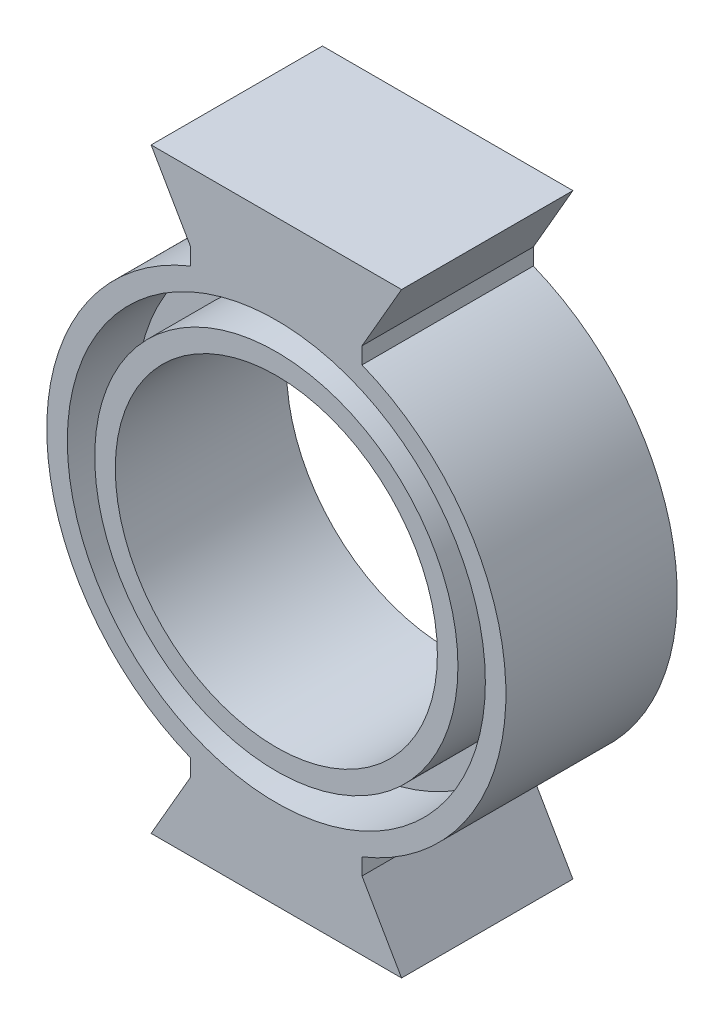
SolidWorks part; units mm, degrees
ref_plane "Front" through (0, 0, 0) normal (0, 0, 1) x (1, 0, 0)
ref_plane "Top" through (0, 0, 0) normal (0, 1, 0) x (1, 0, 0)
ref_plane "Right" through (0, 0, 0) normal (1, 0, 0) x (0, 0, -1)
sketch "Sketch1" plane through (0, 0, 0) normal (0, 0, 1) x (1, 0, 0)
  circle A0 centre (0, 0) radius 5.969
  circle A1 centre (0, 0) radius 8.509
  dimension "D1" = 11.938
  dimension "D2" = 17.018
extrude "Boss-Extrude1" add sketch "Sketch1" along normal blind 6.35
sketch "Sketch2" plane through (0, 0, 6.35) normal (0, 0, 1) x (1, 0, 0)
  circle A0 centre (0, 0) radius 6.731
  circle A1 centre (0, 0) radius 7.747
  dimension "D1" = 13.462
  dimension "D2" = 15.494
extrude "Cut-Extrude1" cut sketch "Sketch2" against normal blind 2.54
sketch "Sketch3" plane through (0, 0, 0) normal (0, 0, 1) x (1, 0, 0)
  line L4 (-3.175, 7.8945) -> (-3.175, 8.509)
  line L5 (3.175, 7.8945) -> (3.175, 8.509)
  line L6 (3.175, 8.509) -> (4.6415, 11.049)
  line L7 (4.6415, 11.049) -> (-4.6415, 11.049)
  line L8 (-4.6415, 11.049) -> (-3.175, 8.509)
  line L9 (-3.175, 8.509) -> (3.175, 8.509) construction
  circle A2 centre (0, 0) radius 8.509 construction
  arc A3 (-3.175, 7.8945) -> (3.175, 7.8945) centre (0, 0) cw
  point P10 (0, 8.509)
  dimension "D1" = 17.018
  dimension "D2" = 6.35
  dimension "D3" = 60
  dimension "D4" = 60
  dimension "D5" = 2.54
extrude "Boss-Extrude2" add sketch "Sketch3" along normal up to surface (6.35 mm away) up to face at (7.747, 0, 6.35)
mirror "Mirror1" about plane through (0, 0, 0) normal (0, 1, 0) of "Boss-Extrude2"
ref_plane "Plane1" through (0, 0, 3.175) normal (0, 0, -1) x (-1, 0, 0)
mirror "Mirror2" about plane through (0, 0, 3.175) normal (0, 0, -1) of "Cut-Extrude1"
